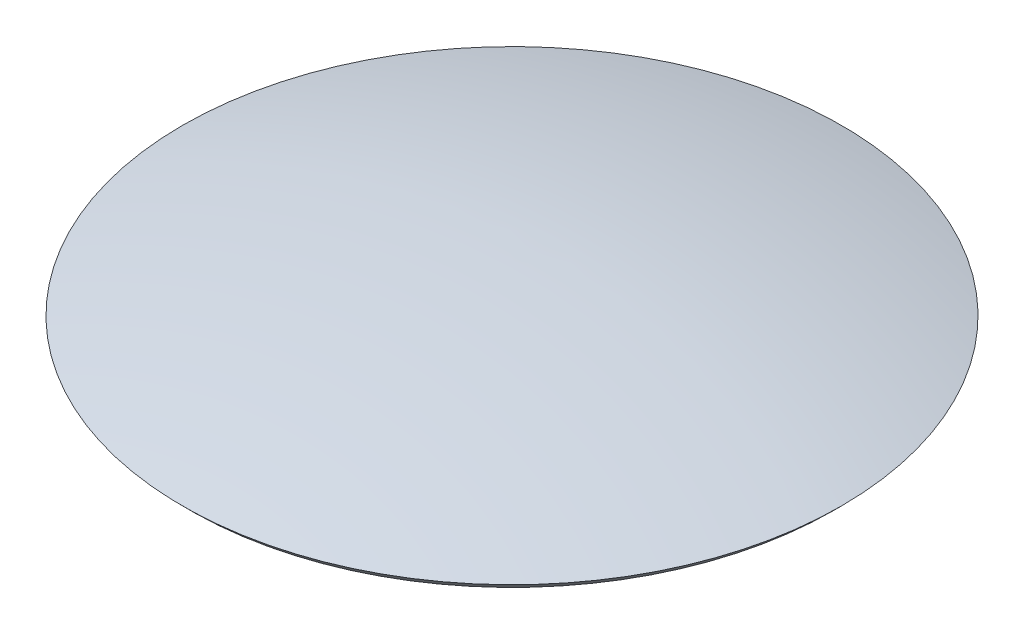
SolidWorks part; units mm, degrees
ref_plane "Front Plane" through (0, 0, 0) normal (0, 0, 1) x (1, 0, 0)
ref_plane "Top Plane" through (0, 0, 0) normal (0, 1, 0) x (1, 0, 0)
ref_plane "Right Plane" through (0, 0, 0) normal (1, 0, 0) x (0, 0, -1)
sketch "Sketch1" plane through (0, 0, 0) normal (0, 0, 1) x (1, 0, 0)
  line L0 (0, 1.5) -> (0, 0)
  line L1 (0, 0) -> (-10, 0)
  arc A0 (0, 1.5) -> (-10, 0) centre (0, -32.5833) ccw
  dimension "D1" = 10
  dimension "D2" = 1.5
revolve "Revolve1" add sketch "Sketch1" angle 360 about L0
chamfer "Chamfer1" distance 1 angle 45 1 edges at (-10, 0, 0) first distance on face at (-10, 0, 0)
